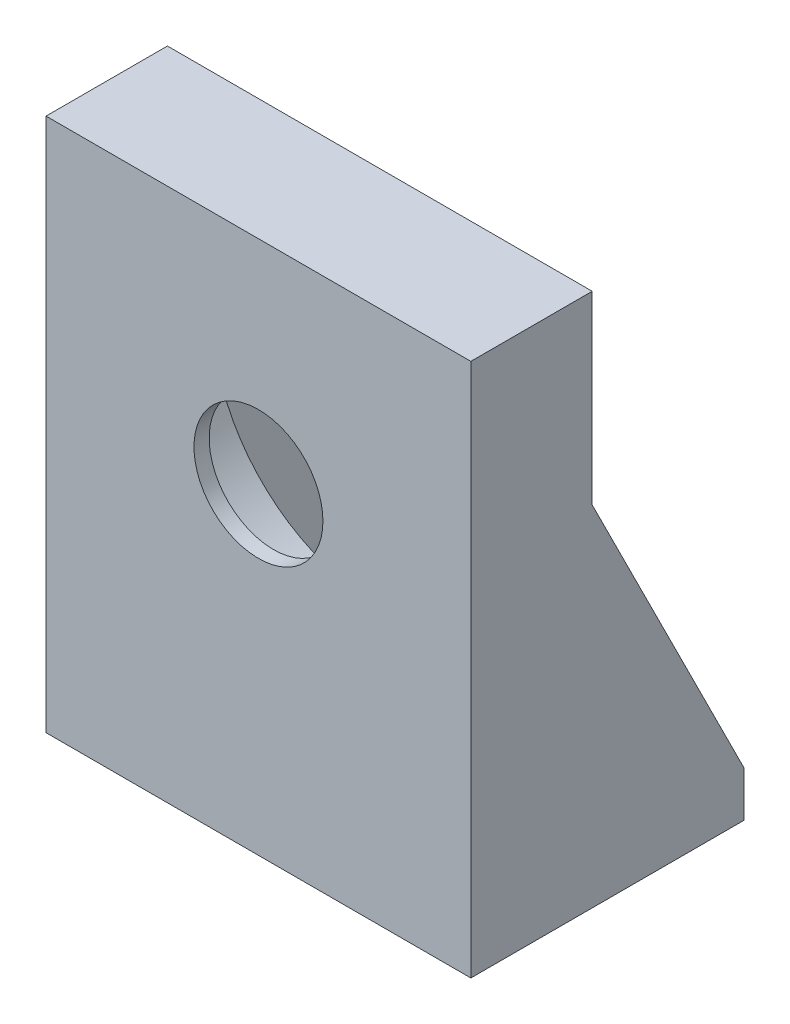
SolidWorks part; units mm, degrees
ref_plane "Front Plane" through (0, 0, 0) normal (0, 0, 1) x (1, 0, 0)
ref_plane "Top Plane" through (0, 0, 0) normal (0, 1, 0) x (1, 0, 0)
ref_plane "Right Plane" through (0, 0, 0) normal (1, 0, 0) x (0, 0, -1)
sketch "Sketch2" plane through (0, 0, -2.5384) normal (0, 0, 1) x (1, 0, 0)
  line L1 (-92.7321, 37.036) -> (-64.7321, 37.036)
  line L2 (-92.7321, 37.036) -> (-92.7321, 1.836)
  line L3 (-92.7321, 1.836) -> (-64.7321, 1.836)
  line L4 (-64.7321, 37.036) -> (-64.7321, 1.836)
  line L5 (-92.7321, 37.036) -> (-64.7321, 1.836) construction
  line L6 (-92.7321, 1.836) -> (-64.7321, 37.036) construction
  line L8 (295.6524, 1.836) -> (-104.3476, 1.836) construction
  line L9 (-78.7321, 37.036) -> (-78.7321, 1.836) construction
  circle A0 centre (-78.7321, 23.036) radius 11
  circle A1 centre (-78.7321, 23.036) radius 4.25
  circle A4 centre (-78.7321, 23.036) radius 4 construction
  point P11 (-78.7321, 19.436)
  circle M1 centre (-78.7321, 23.036) radius 9.65
  circle M2 centre (-78.7321, 23.036) radius 10.7
  dimension "D1" = 22
  dimension "D2" = 8.5
  dimension "D3" = 14
  dimension "D4" = 14
extrude "Boss-Extrude3" add sketch "Sketch2" against normal up to surface (7 mm away) separate body contours L4 L1 L2 L3 A0 region at (-78.7321, 36.5862, -2.5384)
sketch "Sketch3" plane through (-92.7321, 0, 0) normal (-1, 0, 0) x (0, 0, 1)
  line L0 (-9.5384, 1.836) -> (-19.5384, 1.836)
  line L1 (-19.5384, 1.836) -> (-19.5384, 4.836)
  line L2 (-19.5384, 4.836) -> (-9.5384, 24.836)
  line L3 (-9.5384, 1.836) -> (-9.5384, 37.036) construction
  line L5 (-19.5384, 4.836) -> (-9.5384, 4.836)
  line L6 (-9.5384, 4.836) -> (-9.5384, 1.836)
  line L7 (-9.5384, 24.836) -> (-9.5384, 4.836)
  line M3 (-9.5384, 37.036) -> (-9.5384, 1.836)
  dimension "D1" = 3
  dimension "D2" = 20
  dimension "D3" = 10
extrude "Boss-Extrude4" add sketch "Sketch3" against normal up to surface (28 mm away) contours L5 L1 L0 M3 region at (-92.7321, 3.336, -14.5384) up to face at (-64.7321, 19.436, -6.0384)
extrude "Boss-Extrude5" add sketch "Sketch3<3>" against normal blind 3 contours L2 L5 M3 region at (-92.7321, 11.5026, -12.8718)
sketch "Sketch3<3>" plane through (-92.7321, 0, 0) normal (-1, 0, 0) x (0, 0, 1) same geometry as "Sketch3"
extrude "Boss-Extrude6" add sketch "Sketch3<4>" along normal blind 3 from surface contours L2 L5 M3 region at (-92.7321, 11.5026, -12.8718) starting at face at (-64.7321, 14.5693, -10.5384)
sketch "Sketch3<4>" plane through (-92.7321, 0, 0) normal (-1, 0, 0) x (0, 0, 1) same geometry as "Sketch3"
sketch "Sketch4" plane through (0, 4.836, 0) normal (0, 1, 0) x (1, 0, 0)
  line L0 (-67.7321, 14.5384) -> (-89.7321, 14.5384) construction
  line L1 (-67.7321, 19.5384) -> (-67.7321, 9.5384) construction
  line L2 (-89.7321, 19.5384) -> (-89.7321, 9.5384) construction
  line L3 (-78.7321, 9.5384) -> (-78.7321, 19.5384) construction
  line L4 (-67.7321, 9.5384) -> (-89.7321, 9.5384) construction
  line L5 (-67.7321, 19.5384) -> (-89.7321, 19.5384) construction
  line L6 (-67.7321, 14.5384) -> (-78.7321, 14.5384) construction
  line L7 (-78.7321, 14.5384) -> (-89.7321, 14.5384) construction
  circle A0 centre (-72.7321, 14.5384) radius 2
  circle A1 centre (-72.7321, 14.5384) radius 3.5 construction
  circle A2 centre (-84.7321, 14.5384) radius 3.5 construction
  circle A3 centre (-84.7321, 14.5384) radius 2
  dimension "D1" = 4
  dimension "D2" = 7
  dimension "D3" = 6
extrude "Cut-Extrude1" cut sketch "Sketch4" against normal through all
extrude "Boss-Extrude7" add sketch "Sketch2<3>" along normal blind 1 contours L4 L1 L2 L3 A0 | A1 M1 | M2 M1 | A0 M2 region at (-78.7321, 36.5862, -2.5384) region at (-89.701, 23.036, -2.5384) region at (-88.1092, 23.036, -2.5384) region at (-89.1295, 23.036, -2.5384)
sketch "Sketch2<3>" plane through (0, 0, -2.5384) normal (0, 0, 1) x (1, 0, 0) same geometry as "Sketch2"
